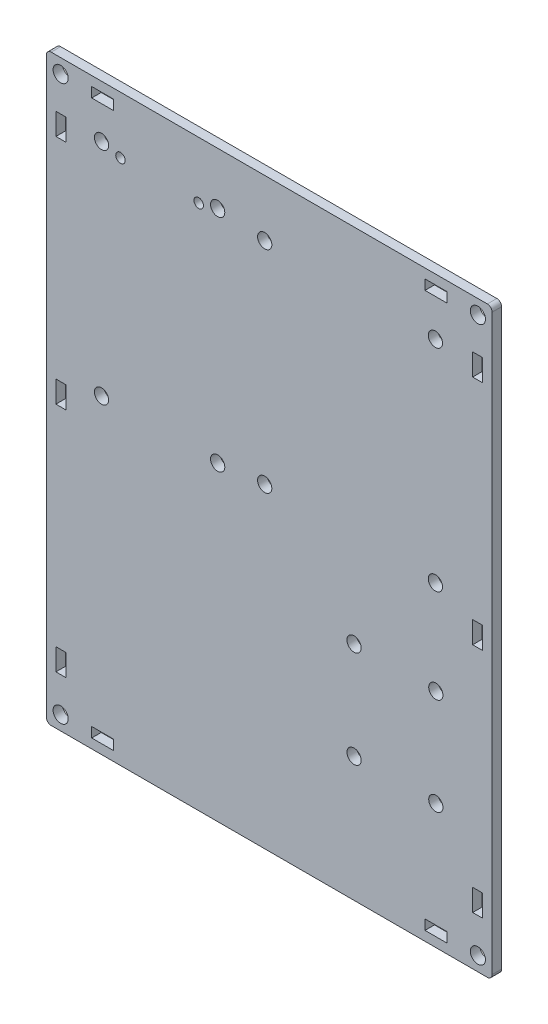
SolidWorks part; units mm, degrees
ref_plane "前基準面" through (0, 0, 0) normal (0, 0, 1) x (1, 0, 0)
ref_plane "上基準面" through (0, 0, 0) normal (0, 1, 0) x (1, 0, 0)
ref_plane "右基準面" through (0, 0, 0) normal (1, 0, 0) x (0, 0, -1)
sketch "Sketch1" plane through (0, 0, 0) normal (0, 0, 1) x (1, 0, 0)
  line L0 (-35.38, 50.5) -> (-47, 50.5) construction
  line L1 (-47, 61.5) -> (47, 61.5)
  line L2 (-47, 61.5) -> (-47, -61.5)
  line L3 (-47, -61.5) -> (47, -61.5)
  line L4 (47, 61.5) -> (47, -61.5)
  line L5 (-47, 61.5) -> (47, -61.5) construction
  line L6 (-47, -61.5) -> (47, 61.5) construction
  line L7 (-47, 50.5) -> (47, 50.5) construction
  line L8 (-35.38, 50.5) -> (-35.38, 61.5) construction
  line L9 (-35.38, 61.5) -> (-35.38, -61.5) construction
  line L10 (-10.88, 50.5) -> (-10.88, 61.5) construction
  line L11 (-10.88, 61.5) -> (-10.88, -61.5) construction
  line L12 (-0.96, 49.58) -> (47, 49.58) construction
  line L13 (-0.96, 49.58) -> (-0.96, 61.5) construction
  line L14 (-0.96, 61.5) -> (-0.96, -61.5) construction
  line L15 (35.04, 49.58) -> (35.04, 61.5) construction
  line L16 (35.04, 61.5) -> (35.04, -61.5) construction
  line L17 (-0.96, 5.08) -> (47, 5.08) construction
  line L18 (0, 0) -> (-45.154, 0) construction
  line L19 (-45.154, 0) -> (47, 0) construction
  line L20 (0, 0) -> (0, 61.5) construction
  line L21 (0, 61.5) -> (0, -61.5) construction
  line L23 (-42.9, 2.3) -> (-45, 2.3)
  line L24 (-42.9, 2.3) -> (-42.9, -2.3)
  line L25 (-42.9, -2.3) -> (-45, -2.3)
  line L26 (-45, 2.3) -> (-45, -2.3)
  line L27 (-42.9, 2.3) -> (-45, -2.3) construction
  line L28 (-42.9, -2.3) -> (-45, 2.3) construction
  line L30 (-45, -46.6) -> (-42.9, -46.6)
  line L31 (-45, 51.2) -> (-42.9, 51.2)
  line L32 (-45, 51.2) -> (-45, 46.6)
  line L33 (-45, 46.6) -> (-42.9, 46.6)
  line L34 (-42.9, 51.2) -> (-42.9, 46.6)
  line L35 (-45, 51.2) -> (-42.9, 46.6) construction
  line L36 (-45, 46.6) -> (-42.9, 51.2) construction
  line L37 (-42.9, -51.2) -> (-42.9, -46.6)
  line L38 (-45, -51.2) -> (-42.9, -51.2)
  line L39 (-45, -51.2) -> (-45, -46.6)
  line L40 (45, 46.6) -> (42.9, 46.6)
  line L41 (42.9, 51.2) -> (42.9, 46.6)
  line L42 (45, 51.2) -> (42.9, 51.2)
  line L43 (45, 51.2) -> (45, 46.6)
  line L44 (45, -51.2) -> (45, -46.6)
  line L45 (45, -51.2) -> (42.9, -51.2)
  line L46 (42.9, -51.2) -> (42.9, -46.6)
  line L47 (45, -46.6) -> (42.9, -46.6)
  line L48 (42.9, -2.3) -> (45, -2.3)
  line L49 (45, 2.3) -> (45, -2.3)
  line L50 (42.9, 2.3) -> (45, 2.3)
  line L51 (42.9, 2.3) -> (42.9, -2.3)
  line L52 (-44, 58.5) -> (44, 58.5) construction
  line L53 (37.45, 57.4) -> (32.85, 57.4)
  line L54 (-37.45, 59.5) -> (-32.85, 59.5)
  line L55 (-37.45, 59.5) -> (-37.45, 57.4)
  line L56 (-37.45, 57.4) -> (-32.85, 57.4)
  line L57 (-32.85, 59.5) -> (-32.85, 57.4)
  line L58 (-37.45, 59.5) -> (-32.85, 57.4) construction
  line L59 (-37.45, 57.4) -> (-32.85, 59.5) construction
  line L60 (32.85, 59.5) -> (32.85, 57.4)
  line L61 (37.45, 59.5) -> (32.85, 59.5)
  line L62 (37.45, 59.5) -> (37.45, 57.4)
  line L63 (37.45, -59.5) -> (37.45, -57.4)
  line L64 (37.45, -59.5) -> (32.85, -59.5)
  line L65 (32.85, -59.5) -> (32.85, -57.4)
  line L66 (37.45, -57.4) -> (32.85, -57.4)
  line L67 (-37.45, -57.4) -> (-32.85, -57.4)
  line L68 (-32.85, -59.5) -> (-32.85, -57.4)
  line L69 (-37.45, -59.5) -> (-32.85, -59.5)
  line L70 (-37.45, -59.5) -> (-37.45, -57.4)
  circle A0 centre (-35.38, 50.5) radius 1.5
  circle A2 centre (-10.88, 50.5) radius 1.5
  circle A3 centre (-35.38, 4) radius 1.5
  circle A4 centre (-10.88, 4) radius 1.5
  circle A5 centre (-0.96, 49.58) radius 1.5
  circle A6 centre (35.04, 49.58) radius 1.5
  circle A7 centre (-0.96, 5.08) radius 1.5
  circle A8 centre (35.04, 5.08) radius 1.5
  circle A9 centre (-44, 58.5) radius 1.6
  circle A10 centre (-44, -58.5) radius 1.6
  circle A11 centre (44, -58.5) radius 1.6
  circle A12 centre (44, 58.5) radius 1.6
  point P0 (0, 0)
  point P47 (-43.95, 0)
  point P54 (-43.95, 48.9)
  point P60 (-35.15, 58.45)
  dimension "D5" = 3
  dimension "D6" = 24.5
  dimension "D7" = 3
  dimension "D9" = 3
  dimension "D10" = 3
  dimension "D15" = 3
  dimension "D16" = 3
  dimension "D18" = 3
  dimension "D19" = 3
  dimension "D20" = 3
  dimension "D22" = 3.2
  dimension "D28" = 48.9
  dimension "D29" = 35.15
  dimension "D1" = 94
  dimension "123" = 123
  dimension "D3" = 11.62
  dimension "D4" = 11
  dimension "D8" = 46.5
  dimension "D11" = 46.5
  dimension "D12" = 9.92
  dimension "D13" = 11.92
  dimension "D14" = 36
  dimension "D17" = 44.5
  dimension "D21" = 4.6
  dimension "D23" = 2.1
  dimension "D24" = 2
  dimension "D25" = 4.6
  dimension "D26" = 2.1
  dimension "D27" = 4.6
  dimension "D30" = 2.1
  dimension "D31" = 2
  dimension "D32" = 3
  dimension "D33" = 2
extrude "Boss-Extrude1" add sketch "Sketch1" along normal blind 2
fillet "Fillet1" radius 1 4 edges at (47, -61.5, 1) (47, 61.5, 1) (-47, 61.5, 1) (-47, -61.5, 1)
sketch "Sketch2" plane through (0, 0, 0) normal (0, 0, -1) x (-1, 0, 0)
  line L0 (31.38, 48.5042) -> (31.38, 50.4958) construction
  line L1 (32.3758, 49.5) -> (30.3842, 49.5) construction
  line L2 (14.88, 48.5042) -> (14.88, 50.4958) construction
  line L3 (15.8758, 49.5) -> (13.8842, 49.5) construction
  arc A0 (31.38, 48.5042) -> (31.38, 50.4958) centre (31.38, 49.5) ccw construction
  arc A1 (31.38, 50.4958) -> (31.38, 48.5042) centre (31.38, 49.5) ccw construction
  arc A2 (14.88, 48.5042) -> (14.88, 50.4958) centre (14.88, 49.5) ccw construction
  arc A3 (14.88, 50.4958) -> (14.88, 48.5042) centre (14.88, 49.5) ccw construction
  circle A4 centre (31.38, 49.5) radius 1
  circle A5 centre (14.88, 49.5) radius 1
  circle A6 centre (-17.8801, -35.1702) radius 1.5
  circle A7 centre (-35.1301, -35.1702) radius 1.5
  circle A8 centre (-17.8801, -14.6698) radius 1.5
  circle A9 centre (-35.1301, -14.6698) radius 1.5
  dimension "D1" = 2
  dimension "D2" = 2
  dimension "D3" = 3
  dimension "D4" = 3
  dimension "D5" = 3
  dimension "D6" = 3
extrude "Cut-Extrude1" cut sketch "Sketch2" against normal blind 10
